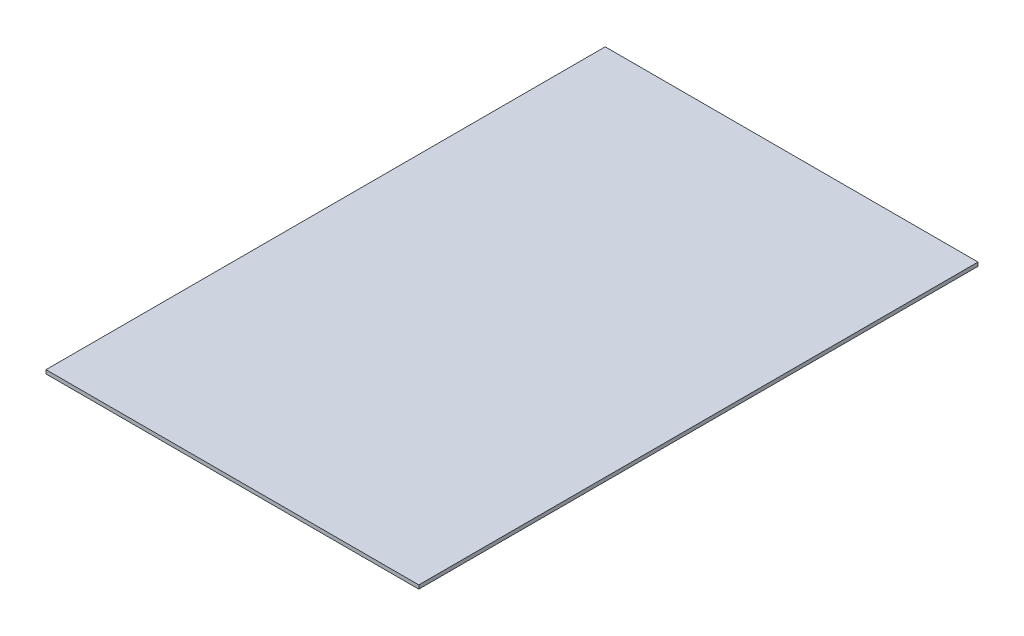
SolidWorks part; units mm, degrees
ref_plane "Płaszczyzna przednia" through (0, 0, 0) normal (0, 0, 1) x (1, 0, 0)
ref_plane "Płaszczyzna górna" through (0, 0, 0) normal (0, 1, 0) x (1, 0, 0)
ref_plane "Płaszczyzna prawa" through (0, 0, 0) normal (1, 0, 0) x (0, 0, -1)
sketch "Szkic1" plane through (0, 0, 0) normal (0, 1, 0) x (1, 0, 0)
  line L1 (-5000, -7500) -> (5000, -7500)
  line L2 (-5000, -7500) -> (-5000, 7500)
  line L3 (-5000, 7500) -> (5000, 7500)
  line L4 (5000, -7500) -> (5000, 7500)
  line L5 (-5000, -7500) -> (5000, 7500) construction
  line L6 (-5000, 7500) -> (5000, -7500) construction
  point P0 (0, 0)
  dimension "D1" = 10000
  dimension "D2" = 15000
extrude "Dodanie-wyciągnięcie1" add sketch "Szkic1" along normal blind 100
